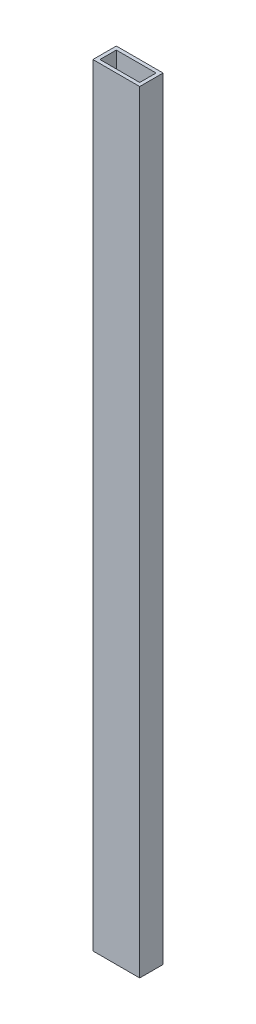
SolidWorks part; units mm, degrees
ref_plane "Front Plane" through (0, 0, 0) normal (0, 0, 1) x (1, 0, 0)
ref_plane "Top Plane" through (0, 0, 0) normal (0, 1, 0) x (1, 0, 0)
ref_plane "Right Plane" through (0, 0, 0) normal (1, 0, 0) x (0, 0, -1)
sketch "Sketch1" plane through (0, 0, 0) normal (0, 1, 0) x (1, 0, 0)
  line L1 (10, -5) -> (-10, -5)
  line L2 (10, -5) -> (10, 5)
  line L3 (10, 5) -> (-10, 5)
  line L4 (-10, -5) -> (-10, 5)
  line L5 (10, -5) -> (-10, 5) construction
  line L6 (10, 5) -> (-10, -5) construction
  point P0 (0, 0)
extrude "Boss-Extrude1" add sketch "Sketch1" along normal up to surface (330 mm away)
sketch "Sketch2" plane through (0, 0, 0) normal (0, -1, 0) x (1, 0, 0)
  line L1 (8.5, 3.5) -> (-8.5, 3.5)
  line L2 (8.5, 3.5) -> (8.5, -3.5)
  line L3 (8.5, -3.5) -> (-8.5, -3.5)
  line L4 (-8.5, 3.5) -> (-8.5, -3.5)
  line L5 (8.5, 3.5) -> (-8.5, -3.5) construction
  line L6 (8.5, -3.5) -> (-8.5, 3.5) construction
  point P0 (0, 0)
extrude "Cut-Extrude1" cut sketch "Sketch2" against normal through all
